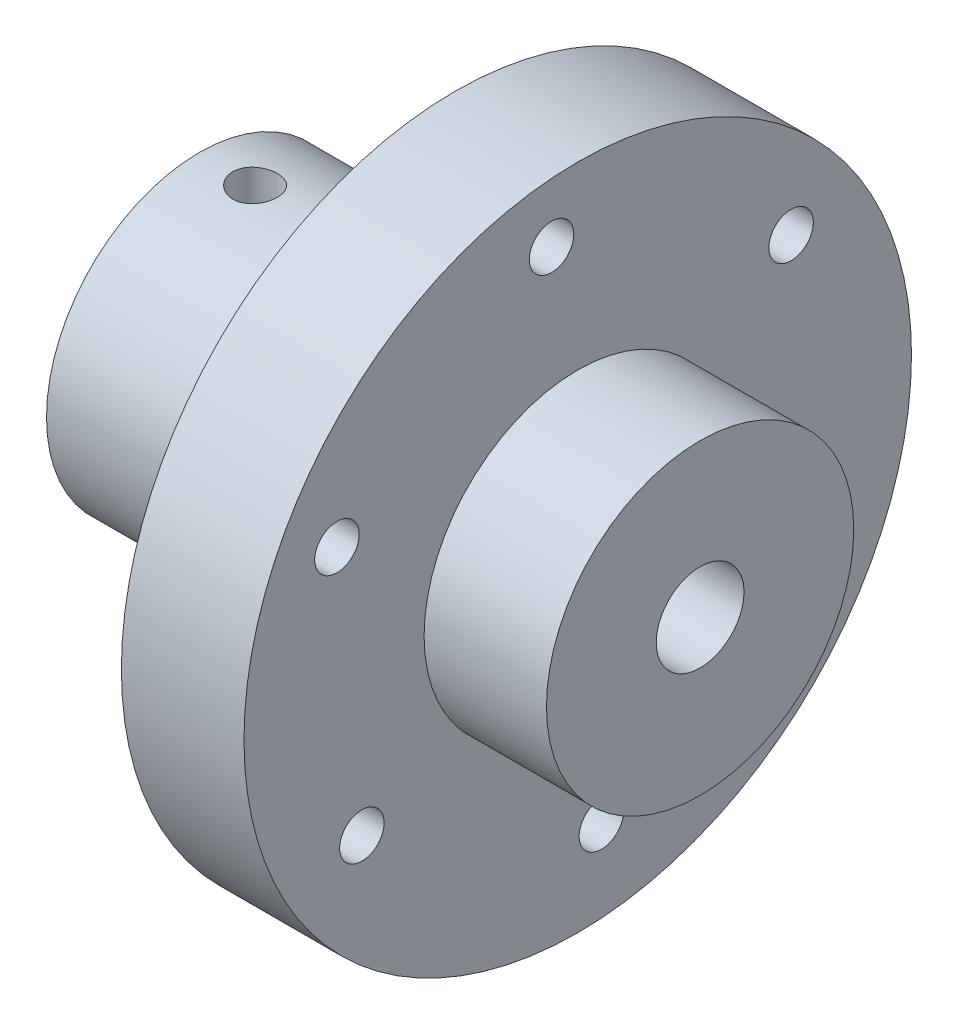
SolidWorks part; units mm, degrees
material "1060 Alloy"
ref_plane "Front" through (0, 0, 0) normal (0, 0, 1) x (1, 0, 0)
ref_plane "Top" through (0, 0, 0) normal (0, 1, 0) x (1, 0, 0)
ref_plane "Right" through (0, 0, 0) normal (1, 0, 0) x (0, 0, -1)
sketch "Sketch1" plane through (0, 0, 0) normal (1, 0, 0) x (0, 0, -1)
  circle A0 centre (0, 0) radius 6
  circle A1 centre (0, 0) radius 13.75
  dimension "D1" = 12
  dimension "D2" = 27.5
extrude "Boss-Extrude1" add sketch "Sketch1" along normal blind 12
sketch "Sketch2" plane through (12, 0, 0) normal (1, 0, 0) x (0, 0, -1)
  circle A0 centre (0, 0) radius 4.01
  circle A1 centre (0, 0) radius 13.75
  dimension "D1" = 8.02
  dimension "D2" = 27.5
extrude "Boss-Extrude3" add sketch "Sketch2" along normal up to surface (10.98 mm away)
sketch "Sketch3" plane through (22.98, 0, 0) normal (1, 0, 0) x (0, 0, -1)
  circle A0 centre (0, 0) radius 30
  dimension "D1" = 60
extrude "Boss-Extrude4" add sketch "Sketch3" along normal up to surface (11.02 mm away)
sketch "Sketch4" plane through (34, 0, 0) normal (1, 0, 0) x (0, 0, -1)
  point P0 (19.1785, 14.7249)
  point P1 (21.4196, -8.8438)
  point P3 (-2.3532, 24.5684)
  point P5 (-21.6437, 10.8432)
  point P7 (-19.4025, -12.7255)
  point P9 (2.1291, -22.569)
hole_wizard "Ø4.0mm Dowel Hole1" positions "Sketch5" profile "Sketch6" hole size "Ø4.0" standard "ANSI Metric"
sketch "Sketch5" plane through (34, 0, 0) normal (1, 0, 0) x (0, 0, -1)
  point P0 (-21.6437, 10.8432)
  point P3 (-2.3532, 24.5684)
  point P6 (19.1785, 14.7249)
  point P9 (21.4196, -8.8438)
  point P12 (-19.4025, -12.7255)
  point P15 (2.1291, -22.569)
sketch "Sketch6" plane through (34, 10.8432, 21.6437) normal (0, 1, 0) x (0, 0, -1)
  line L0 (0, 0) -> (0, 26.6017)
  line L1 (0, 26.6017) -> (2, 25.4)
  line L2 (2, 25.4) -> (2, 0)
  line L5 (2, 0) -> (0, 0)
  line L10 (0, 26.6017) -> (-2, 25.4) construction
  line L11 (0, -6.35) -> (0, 107.95) construction
  dimension "Hole Dia." = 4
  dimension "Hole Depth" = 25.4
  dimension "Drill Angle" = 118
ref_plane "Plane1" through (0, 13.5, 0) normal (0, 1, 0) x (-1, 0, 0)
sketch "Sketch11" plane through (0, 0, 0) normal (-1, 0, 0) x (0, 0, 1)
  line L1 (2.025, 3.85) -> (-2.025, 3.85)
  line L2 (2.025, 3.85) -> (2.025, 8.15)
  line L3 (2.025, 8.15) -> (-2.025, 8.15)
  line L4 (-2.025, 3.85) -> (-2.025, 8.15)
  line L5 (0, 8.15) -> (0, 3.85) construction
  line L6 (2.025, 6) -> (-2.025, 6) construction
  circle A0 centre (0, 0) radius 6 construction
  circle A1 centre (0, 0) radius 6 construction
  point P0 (0, 6)
  dimension "D1" = 8.15
  dimension "D2" = 4.05
extrude "Cut-Extrude1" cut sketch "Sketch11" against normal blind 10
sketch "Sketch12" plane through (0, 8.15, 0) normal (0, -1, 0) x (1, 0, 0)
  point P0 (5, 0)
hole_wizard "Ø4.0mm Dowel Hole2" positions "Sketch13" profile "Sketch14" hole size "Ø4.0" standard "ANSI Metric"
sketch "Sketch13" plane through (0, 8.15, 0) normal (0, -1, 0) x (-1, 0, 0)
  point P0 (-5, 0)
sketch "Sketch14" plane through (5, 8.15, 0) normal (1, 0, 0) x (0, 0, -1)
  line L0 (0, 0) -> (0, 26.6017)
  line L1 (0, 26.6017) -> (2, 25.4)
  line L2 (2, 25.4) -> (2, 0)
  line L5 (2, 0) -> (0, 0)
  line L10 (0, 26.6017) -> (-2, 25.4) construction
  line L11 (0, -6.35) -> (0, 107.95) construction
  dimension "Hole Dia." = 4
  dimension "Hole Depth" = 25.4
  dimension "Drill Angle" = 118
sketch "Sketch15" plane through (34, 0, 0) normal (1, 0, 0) x (0, 0, -1)
  circle A0 centre (0, 0) radius 4.01
  dimension "D1" = 8.02
extrude "Cut-Extrude2" cut sketch "Sketch15" against normal blind 32
sketch "Sketch16" plane through (34, 0, 0) normal (1, 0, 0) x (0, 0, -1)
  circle A0 centre (0, 0) radius 13.8107
  circle A1 centre (0, 0.0565) radius 3.9435
extrude "Boss-Extrude5" add sketch "Sketch16" along normal up to surface (11 mm away)
